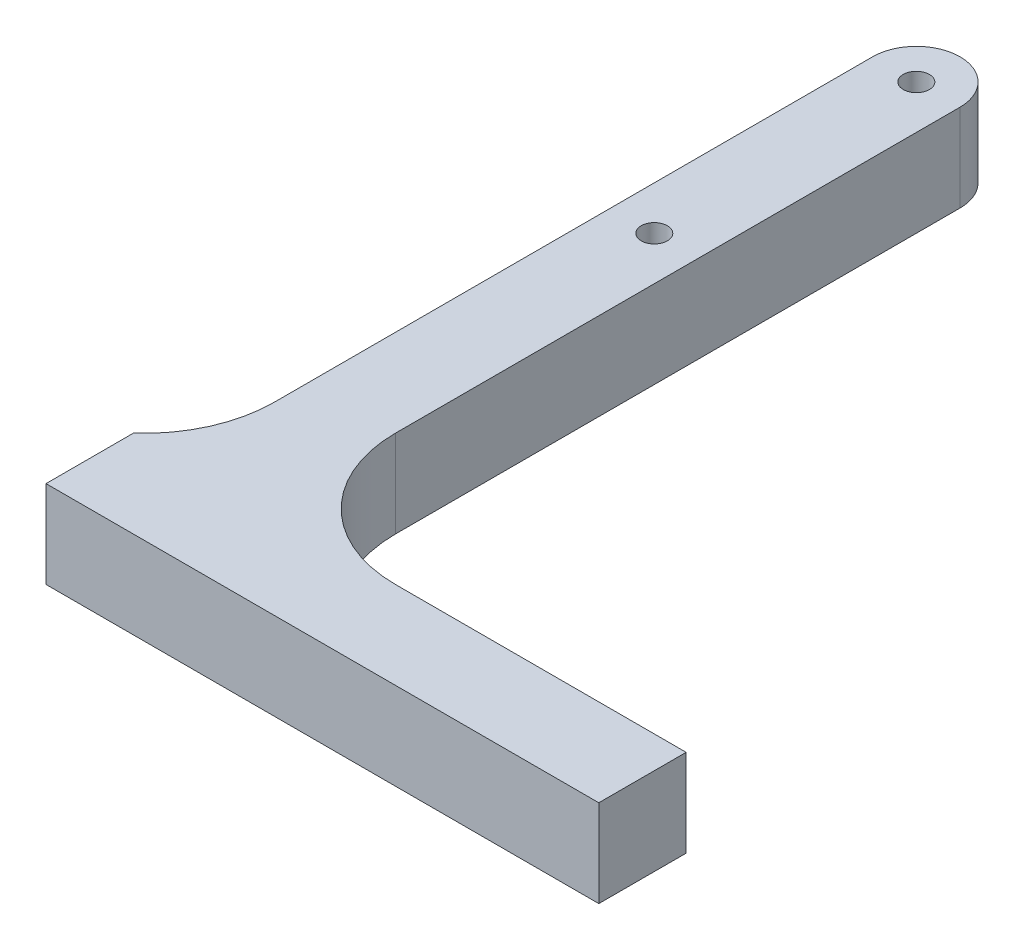
SolidWorks part; units mm, degrees
ref_plane "Front Plane" through (0, 0, 0) normal (0, 0, 1) x (1, 0, 0)
ref_plane "Top Plane" through (0, 0, 0) normal (0, 1, 0) x (1, 0, 0)
ref_plane "Right Plane" through (0, 0, 0) normal (1, 0, 0) x (0, 0, -1)
sketch "Sketch1" plane through (0, 0, 0) normal (0, 1, 0) x (1, 0, 0)
  line L0 (10, 0) -> (10, 10) construction
  line L1 (0, 0) -> (10, 0)
  line L2 (0, 10) -> (0, 89.63)
  line L3 (0, 89.63) -> (10, 89.63) construction
  line L4 (10, 10) -> (10, 89.63)
  line L5 (10, 0) -> (58.28, 0)
  line L6 (10, 0) -> (10, 10) construction
  line L7 (10, 10) -> (58.28, 10)
  line L8 (58.28, 0) -> (58.28, 10)
  line L9 (0, 10) -> (-5, 10)
  line L10 (0, 10) -> (0, 0) construction
  line L11 (0, 0) -> (-5, 0)
  line L12 (-5, 10) -> (-5, 0)
  line L13 (0, 0) -> (0, 10) construction
  arc A0 (0, 89.63) -> (10, 89.63) centre (5, 89.63) cw
  dimension "D1" = 10
  dimension "D2" = 89.63
  dimension "D3" = 10
  dimension "D4" = 5
  dimension "D5" = 48.28
extrude "Boss-Extrude1" add sketch "Sketch1" along normal blind 10
sketch "Sketch2" plane through (0, 10, 0) normal (0, 1, 0) x (1, 0, 0)
  circle A0 centre (5, 89.63) radius 1.5
  circle A1 centre (5, 59.63) radius 1.5
  dimension "D1" = 3
  dimension "D2" = 30
extrude "Cut-Extrude1" cut sketch "Sketch2" against normal through all
sketch "Sketch4" plane through (0, 10, 0) normal (0, 1, 0) x (1, 0, 0)
  line L0 (0, 33.93) -> (10, 33.93) construction
  line L1 (0, 89.63) -> (0, 10) construction
  line L2 (10, 10) -> (10, 89.63) construction
  text T0 "<b>R</b>" font "Century Gothic" height 8
extrude "Boss-Extrude2" add sketch "Sketch4" along normal blind 0.5
sketch "Sketch5" plane through (0, 10, 0) normal (0, 1, 0) x (1, 0, 0)
  circle A0 centre (5, 89.63) radius 3.25
  circle A1 centre (5, 59.63) radius 3.25
  dimension "D1" = 6.5
extrude "Cut-Extrude2" cut sketch "Sketch5" against normal offset from surface (5 mm away) 5 up to face at (5, 0, -88.13)
mirror "Mirror1" about plane through (0, 0, 0) normal (0, 1, 0) of bodies 104
delete or keep bodies "Body-Delete/Keep 1" type delete bodies bodies 104
fillet "Fillet1" radius 15 2 edges at (0, -5, -10) (10, -5, -10)
